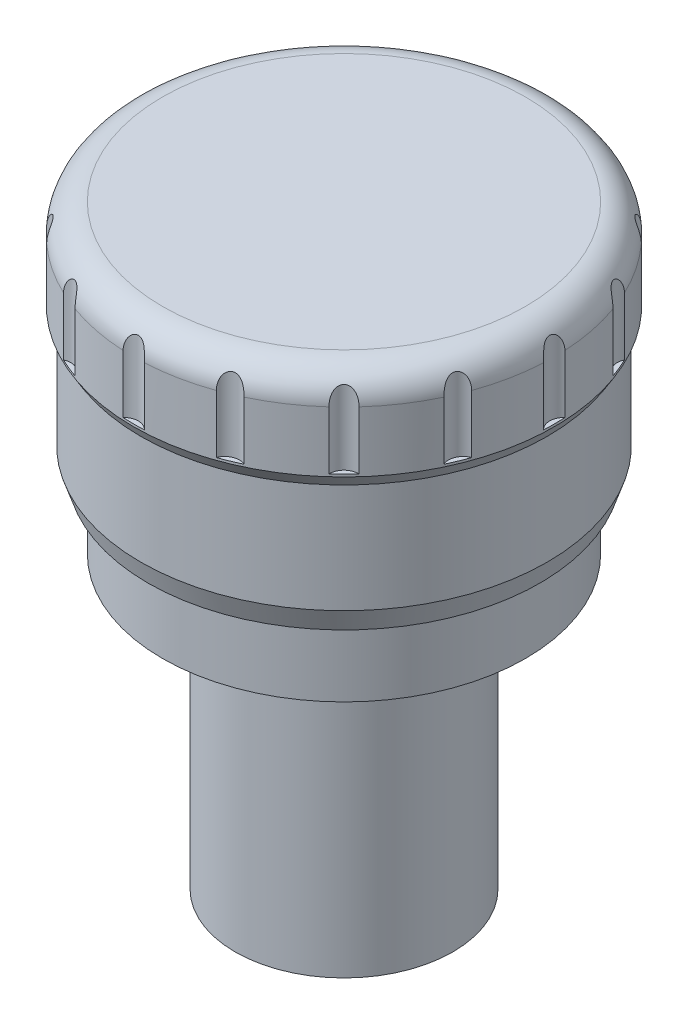
SolidWorks part; units mm, degrees
material "ABS"
ref_plane "Front Plane" through (0, 0, 0) normal (0, 0, 1) x (1, 0, 0)
ref_plane "Top Plane" through (0, 0, 0) normal (0, 1, 0) x (1, 0, 0)
ref_plane "Right Plane" through (0, 0, 0) normal (1, 0, 0) x (0, 0, -1)
sketch "Sketch1" plane through (0, 0, 0) normal (0, 1, 0) x (1, 0, 0)
  circle A0 centre (0, 0) radius 12.5
  dimension "D1" = 25
extrude "Boss-Extrude1" add sketch "Sketch1" along normal blind 5
sketch "Sketch2" plane through (0, 0, 0) normal (0, -1, 0) x (1, 0, 0)
  circle A0 centre (0, 0) radius 7.5
  dimension "D1" = 15
extrude "Boss-Extrude2" add sketch "Sketch2" along normal blind 20
sketch "Sketch3" plane through (0, 5, 0) normal (0, 1, 0) x (1, 0, 0)
  circle A0 centre (0, 0) radius 14
  dimension "D1" = 28
extrude "Boss-Extrude3" add sketch "Sketch3" along normal blind 9
chamfer "Chamfer1" distance 0.5 distance2 1.5 1 edges at (0, 5, 14) first distance on face at (0, 5, 14)
sketch "Sketch4" plane through (0, 14, 0) normal (0, 1, 0) x (1, 0, 0)
  circle A0 centre (0, 0) radius 14.5
  dimension "D1" = 29
extrude "Boss-Extrude4" add sketch "Sketch4" along normal blind 7
fillet "Fillet3" radius 2 1 edges at (0, 21, 14.5) type face fillet first side face at (0, 21, 14.5) second side face at (0, 21, 14.5)
chamfer "Chamfer2" distance 0.5 angle 59 1 edges at (0, 14, 14.5) first distance on face at (0, 14, 14.5)
sketch "Sketch5" plane through (0, 21, 0) normal (0, 1, 0) x (1, 0, 0)
  line L0 (-0.75, 14.5) -> (0.75, 14.5)
  line L1 (0, 0) -> (0, 14.5) construction
  arc A0 (-0.75, 14.5) -> (0.75, 14.5) centre (0, 15.1614) ccw
  circle A1 centre (0, 0) radius 14.5 construction
  dimension "D2" = 1
  dimension "D1" = 1.5
extrude "Cut-Extrude2" cut sketch "Sketch5" against normal blind 6
ref_axis "Axis1" through (0, 23.05, 0) along (0, -1, 0)
pattern_circular "CirPattern1" count 16 over 360 about axis through (0, 23.05, 0) along (0, -1, 0) of "Cut-Extrude2"
